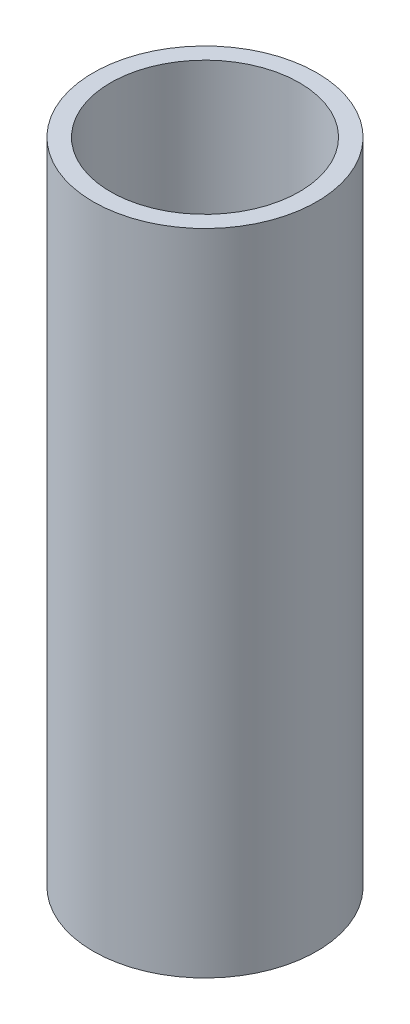
SolidWorks part; units mm, degrees
ref_plane "Front Plane" through (0, 0, 0) normal (0, 0, 1) x (1, 0, 0)
ref_plane "Top Plane" through (0, 0, 0) normal (0, 1, 0) x (1, 0, 0)
ref_plane "Right Plane" through (0, 0, 0) normal (1, 0, 0) x (0, 0, -1)
sketch "Sketch1" plane through (0, 0, 0) normal (0, 1, 0) x (1, 0, 0)
  circle A0 centre (0, 0) radius 20
  dimension "SLEEVE_OD" = 40
extrude "Boss-Extrude1" add sketch "Sketch1" along normal blind 116.1306
sketch "Sketch2" plane through (0, 0, 0) normal (0, 1, 0) x (1, 0, 0)
  circle A0 centre (0, 0) radius 16.8988
  dimension "BORE_D" = 33.7976
extrude "Cut-Extrude1" cut sketch "Sketch2" along normal through all
chamfer "Chamfer1" distance 3.9322 angle 27.082 rebuild error yes
